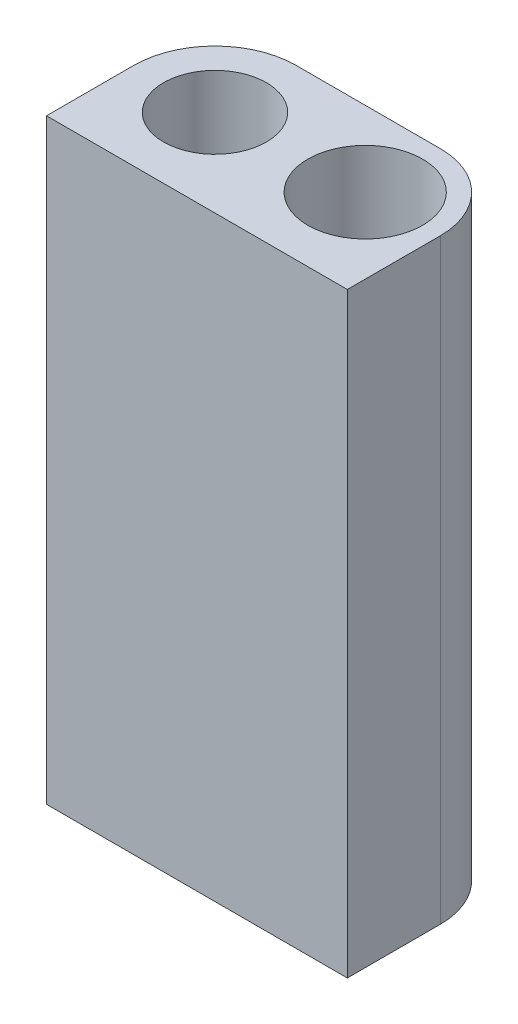
SolidWorks part; units mm, degrees
ref_plane "Front Plane" through (0, 0, 0) normal (0, 0, 1) x (1, 0, 0)
ref_plane "Top Plane" through (0, 0, 0) normal (0, 1, 0) x (1, 0, 0)
ref_plane "Right Plane" through (0, 0, 0) normal (1, 0, 0) x (0, 0, -1)
sketch "Sketch1" plane through (0, 0, 0) normal (0, 1, 0) x (1, 0, 0)
  line L0 (0, -55) -> (0, 55) construction
  line L1 (-5.45, 0) -> (3.45, 0)
  line L2 (-5.45, 0) -> (-5.45, -5.85)
  line L3 (-5.45, -5.85) -> (5.45, -5.85)
  line L5 (3.45, 0) -> (5.85, 0) construction
  line L6 (0, 5.45) -> (9.6792, 5.45)
  line L7 (14.7292, 0.4) -> (14.7292, -5.85)
  line L8 (14.7292, -5.85) -> (5.45, -5.85)
  line L10 (0, -3.45) -> (9.6792, -3.45) construction
  line L11 (0, -3.45) -> (0, -5.85)
  circle A0 centre (0, 0) radius 3.45
  circle A2 centre (9.6792, 0.4) radius 3.85
  arc A3 (14.7292, 0.4) -> (9.6792, 5.45) centre (9.6792, 0.4) ccw
  arc A4 (0, 5.45) -> (-5.45, 0) centre (0, 0) ccw
  point P8 (0, -5.85)
  dimension "D1" = 6.9
  dimension "D2" = 2.4
  dimension "D3" = 7.7
  dimension "D4" = 10.1
  dimension "D5" = 2.4
extrude "Boss-Extrude2" add sketch "Sketch1" along normal blind 40 contours L6 A4 L1 A0 L11 L3 L8 L7 A3 A2 | A0 L1 L2 L3 L11 region at (5.7707, 0, 0.3218) region at (-3.248, 0, 3.531)
